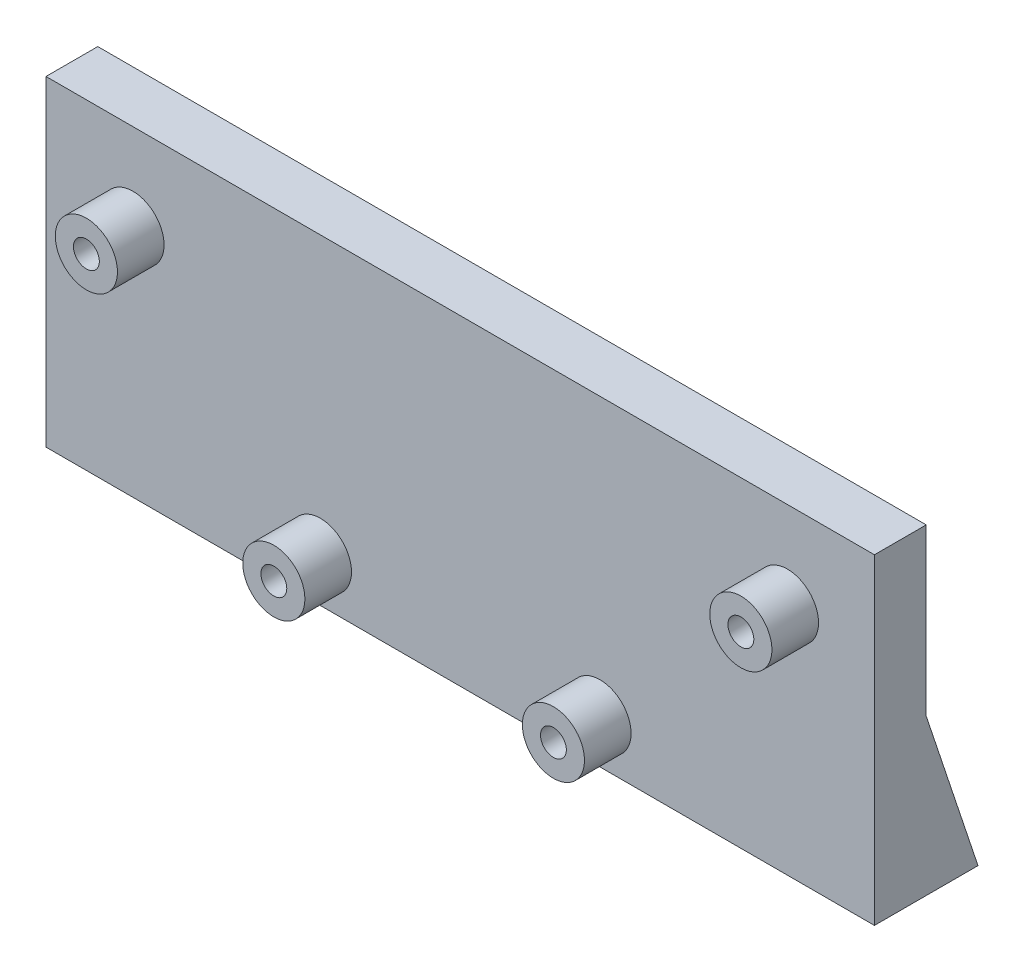
SolidWorks part; units mm, degrees
ref_plane "Plan de face" through (0, 0, 0) normal (0, 0, 1) x (1, 0, 0)
ref_plane "Plan de dessus" through (0, 0, 0) normal (0, 1, 0) x (1, 0, 0)
ref_plane "Plan de droite" through (0, 0, 0) normal (1, 0, 0) x (0, 0, -1)
sketch "Esquisse1" plane through (0, 0, 0) normal (0, 0, 1) x (1, 0, 0)
  line L1 (-40, 15.5) -> (0, 15.5)
  line L2 (-40, 15.5) -> (-40, -15.5)
  line L3 (-40, -15.5) -> (0, -15.5)
  line L4 (0, 15.5) -> (0, -15.5)
  point P4 (-20, 15.5)
  point P5 (0, 0)
  dimension "D1" = 31
  dimension "D2" = 40
extrude "Boss.-Extru.1" add sketch "Esquisse1" along normal blind 5
sketch "Esquisse2" plane through (0, 0, 5) normal (0, 0, 1) x (1, 0, 0)
  line L0 (-40, 15.5) -> (-40, -15.5) construction
  line L1 (0, 15.5) -> (-40, 15.5) construction
  line L2 (-40, -15.5) -> (0, -15.5) construction
  circle A0 centre (-31.6, 7.1) radius 3
  circle A1 centre (-13.5, -11.2) radius 3
  circle A2 centre (-31.6, 7.1) radius 1.25
  circle A3 centre (-13.5, -11.2) radius 1.25
  dimension "D1" = 8.4
  dimension "D3" = 6
  dimension "D4" = 26.5
  dimension "D6" = 2.5
  dimension "D7" = 2.5
  dimension "D2" = 8.4
  dimension "D5" = 4.3
extrude "Boss.-Extru.2" add sketch "Esquisse2" along normal mid plane 9
sketch "Esquisse4" plane through (0, 0, 0) normal (1, 0, 0) x (0, 0, -1)
  line L0 (0, -15.5) -> (0, -0.5)
  line L1 (0, -15.5) -> (0, 15.5) construction
  line L2 (0, -0.5) -> (5, -15.5)
  line L3 (5, -15.5) -> (0, -15.5)
  dimension "D1" = 5
  dimension "D2" = 15
extrude "Boss.-Extru.3" add sketch "Esquisse4" against normal up to surface (40 mm away) up to face at (-40, 0, 2.5)
sketch "Esquisse5" plane through (0, -15.5, 0) normal (0, -1, 0) x (1, 0, 0)
  line L0 (-40, 5) -> (0, 5) construction
  line L1 (-40, -5) -> (0, -5) construction
  circle A0 centre (-20, 2) radius 1.25
  circle A1 centre (-20, -2) radius 1.25
  point P2 (-20, 5)
  point P7 (-20, -5)
  dimension "D1" = 2.5
  dimension "D3" = 3
  dimension "D2" = 3
extrude "Enlèv. mat.-Extru.1" cut sketch "Esquisse5" against normal blind 16
mirror "Symétrie1" about plane through (0, 0, 0) normal (1, 0, 0) of "Enlèv. mat.-Extru.1", "Boss.-Extru.1", "Boss.-Extru.2", "Boss.-Extru.3"
